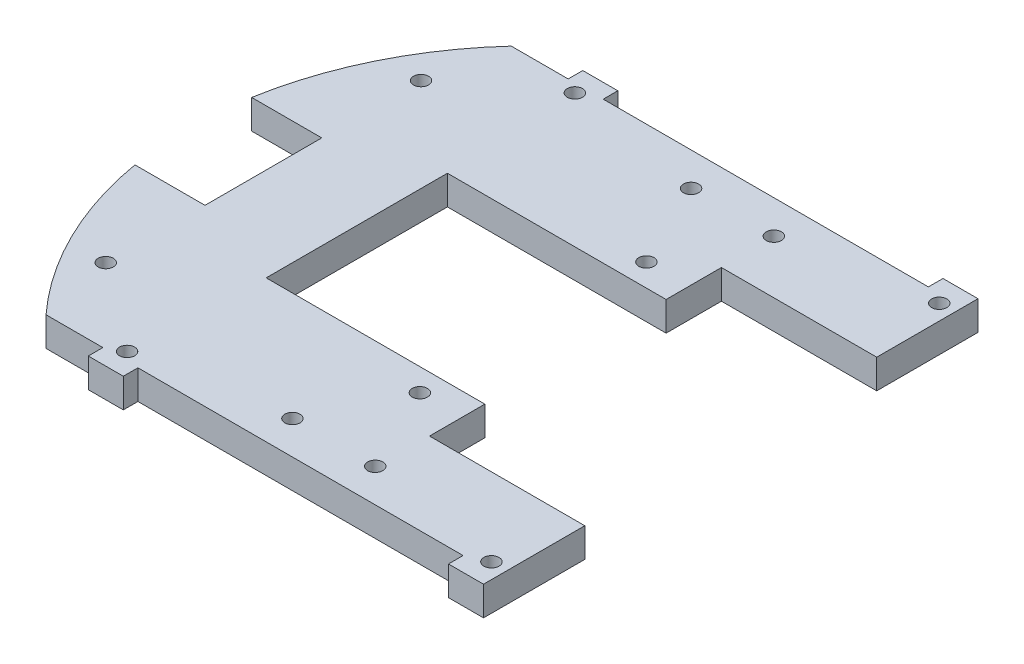
SolidWorks part; units mm, degrees
material "Acrylic (Medium-high impact)"
ref_plane "Front Plane" through (0, 0, 0) normal (0, 0, 1) x (1, 0, 0)
ref_plane "Top Plane" through (0, 0, 0) normal (0, 1, 0) x (1, 0, 0)
ref_plane "Right Plane" through (0, 0, 0) normal (1, 0, 0) x (0, 0, -1)
sketch "Sketch1" plane through (0, 0, 0) normal (0, 1, 0) x (1, 0, 0)
  line L0 (33.7767, 5.8989) -> (4.6272, 5.8989)
  line L1 (-30.9328, 38.3108) -> (-15.6928, 38.3108)
  line L2 (-15.6928, 38.3108) -> (-15.6928, 12.9108)
  line L3 (7.62, -24.9927) -> (78.3483, -24.9927)
  line L4 (33.7767, 5.8989) -> (52.1917, 5.8989)
  line L5 (52.1917, 5.8989) -> (52.1917, -6.1392)
  line L6 (52.1917, -6.1392) -> (85.9683, -6.1392)
  line L7 (85.9683, -6.1392) -> (85.9683, -24.9927)
  line L8 (42.9842, 0.9728) -> (42.9842, 5.8989) construction
  line L9 (82.6111, -23.0877) -> (82.6111, -6.1392) construction
  line L10 (82.6111, -23.0877) -> (85.9683, -23.0877) construction
  line L11 (3.3572, -23.0877) -> (3.3572, -6.1392) construction
  line L12 (3.3572, -23.0877) -> (0, -23.0877) construction
  line L13 (0, 76.2143) -> (0, 79.3893)
  line L14 (7.62, 76.2143) -> (7.62, 79.3893)
  line L15 (-30.9328, 25.6108) -> (90.9164, 25.6108) construction
  line L16 (-30.9328, 38.3108) -> (-30.9328, 12.9108) construction
  line L17 (90.9164, 24.0233) -> (90.9164, 27.1983) construction
  line L18 (3.3572, 74.3093) -> (0, 74.3093) construction
  line L19 (3.3572, 74.3093) -> (3.3572, 57.3608) construction
  line L20 (82.6111, 74.3093) -> (85.9683, 74.3093) construction
  line L21 (82.6111, 74.3093) -> (82.6111, 57.3608) construction
  line L22 (42.9842, 50.2488) -> (42.9842, 45.3227) construction
  line L23 (85.9683, 57.3608) -> (85.9683, 76.2143)
  line L24 (52.1917, 57.3608) -> (85.9683, 57.3608)
  line L25 (52.1917, 45.3227) -> (52.1917, 57.3608)
  line L26 (33.7767, 45.3227) -> (52.1917, 45.3227)
  line L27 (7.62, 76.2143) -> (78.3483, 76.2143)
  line L28 (-15.6928, 12.9108) -> (-30.9328, 12.9108)
  line L30 (33.7767, 45.3227) -> (4.6272, 45.3227)
  line L31 (78.3483, 76.2143) -> (78.3483, 79.3893)
  line L32 (0, 76.2143) -> (-12.3719, 76.2143)
  line L33 (4.6272, 45.3227) -> (4.6272, 5.8989)
  line L34 (0, -24.9927) -> (-12.3719, -24.9927)
  line L35 (78.3483, 79.3893) -> (85.9683, 79.3893)
  line L36 (85.9683, 76.2143) -> (85.9683, 79.3893)
  line L37 (7.62, 79.3893) -> (0, 79.3893)
  line L38 (78.3483, -24.9927) -> (78.3483, -28.1677)
  line L39 (85.9683, -24.9927) -> (85.9683, -28.1677)
  line L40 (78.3483, -28.1677) -> (85.9683, -28.1677)
  line L41 (7.62, -24.9927) -> (7.62, -28.1677)
  line L42 (0, -24.9927) -> (0, -28.1677)
  line L43 (7.62, -28.1677) -> (0, -28.1677)
  circle A0 centre (3.3572, -23.0877) radius 1.651
  circle A1 centre (82.6111, -23.0877) radius 1.651
  circle A2 centre (42.9842, 0.9728) radius 1.651
  circle A3 centre (33.9834, -17.7427) radius 1.651
  circle A4 centre (51.9834, -17.7427) radius 1.651
  circle A5 centre (42.9842, 0.9728) radius 1.651 construction
  circle A6 centre (51.9834, 68.9643) radius 1.651
  circle A7 centre (33.9834, 68.9643) radius 1.651
  circle A8 centre (42.9842, 50.2488) radius 1.651
  circle A9 centre (82.6111, 74.3093) radius 1.651
  circle A10 centre (3.3572, 74.3093) radius 1.651
  arc A11 (-30.9328, 12.9108) -> (110.2551, -7.5497) centre (42.9842, 25.6108) ccw construction
  arc A12 (-12.3719, 76.2143) -> (-30.9328, 38.3108) centre (42.9842, 25.6108) ccw
  arc A13 (110.2551, 58.7714) -> (-30.9328, 38.3108) centre (42.9842, 25.6108) ccw construction
  arc A14 (-12.3719, -24.9927) -> (-30.9328, 12.9108) centre (42.9842, 25.6108) cw
  circle A15 centre (-15.6928, 59.9008) radius 1.651
  circle A16 centre (-15.6928, -8.6792) radius 1.651
  circle A17 centre (-15.6928, 59.9008) radius 1.651 construction
  dimension "D1" = 33.7767
  dimension "D2" = 63.5
  dimension "D3" = 4.9261
  dimension "D4" = 20.32
  dimension "D5" = 116.9011
  dimension "D6" = 3.175
  dimension "D7" = 7.62
extrude "Boss-Extrude1" add sketch "Sketch1" along normal blind 6.35
